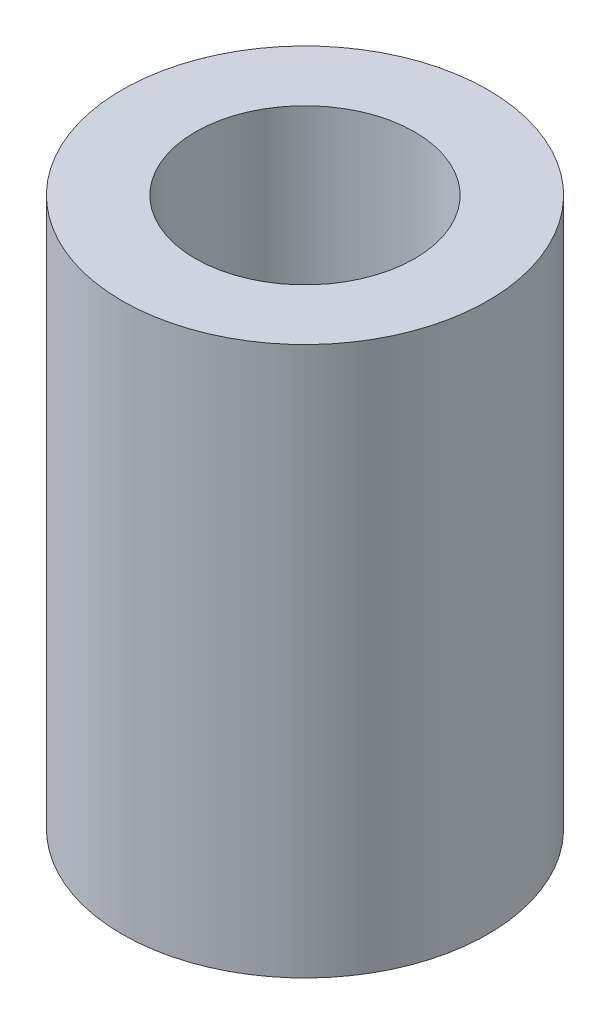
SolidWorks part; units mm, degrees
ref_plane "前视基准面" through (0, 0, 0) normal (0, 0, 1) x (1, 0, 0)
ref_plane "上视基准面" through (0, 0, 0) normal (0, 1, 0) x (1, 0, 0)
ref_plane "右视基准面" through (0, 0, 0) normal (1, 0, 0) x (0, 0, -1)
sketch "草图1" plane through (0, 0, 0) normal (0, 1, 0) x (1, 0, 0)
  circle A0 centre (0, 0) radius 3
  circle A1 centre (0, 0) radius 5
extrude "凸台-拉伸1" add sketch "草图1" along normal blind 15
